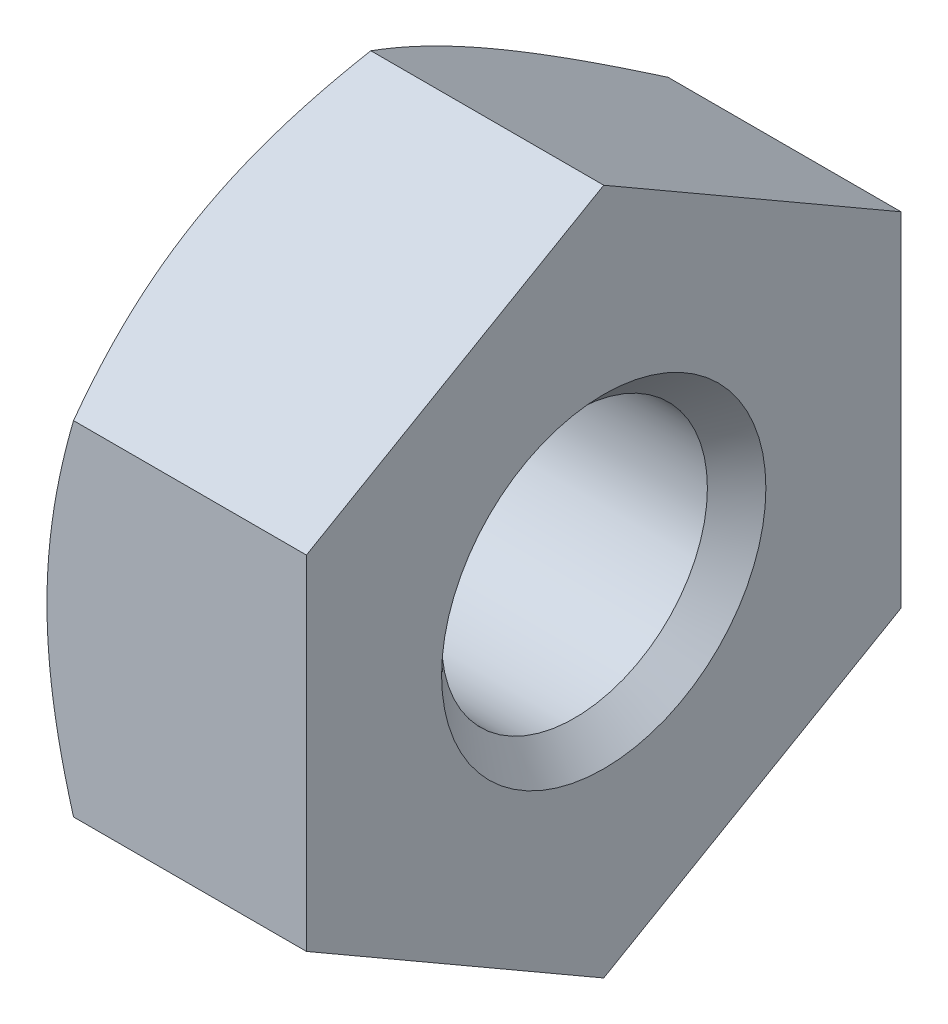
SolidWorks part; units mm, degrees
material "AISI 304"
ref_plane "正面" through (0, 0, 0) normal (0, 0, 1) x (1, 0, 0)
ref_plane "平面" through (0, 0, 0) normal (0, 1, 0) x (1, 0, 0)
ref_plane "右側面" through (0, 0, 0) normal (1, 0, 0) x (0, 0, -1)
ref_plane "Plane1" through (0, 0, 0) normal (0, 0, 1) x (1, 0, 0)
sketch "Sketch1" plane through (0, 0, 0) normal (0, 0, 1) x (1, 0, 0)
  line L0 (-1.2, 0) -> (-1.2, 2.75)
  line L1 (-1.2, 2.75) -> (-0.9402, 3.2)
  line L2 (-0.9402, 3.2) -> (1.2, 3.2)
  line L3 (1.2, 3.2) -> (1.2, 0)
  line L4 (1.2, 0) -> (-1.2, 0)
  line L5 (1.2, 0) -> (-1.2, 0) construction
revolve "Revolve1" add sketch "Sketch1" angle 360 about L5 reverse direction yes
ref_plane "Plane2" through (0, 0, 0) normal (0, 0, 1) x (1, 0, 0)
sketch "Sketch2" plane through (0, 0, 0) normal (0, 0, 1) x (1, 0, 0)
  line L0 (-1.2, 0) -> (-1.2, 1.5)
  line L1 (-1.2, 1.5) -> (-0.9295, 1.2295)
  line L2 (-0.9295, 1.2295) -> (0.9295, 1.2295)
  line L3 (0.9295, 1.2295) -> (1.2, 1.5)
  line L4 (1.2, 1.5) -> (1.2, 0)
  line L5 (1.2, 0) -> (-1.2, 0)
  line L6 (1.2, 0) -> (-1.2, 0) construction
revolve "Cut-Revolve1" cut sketch "Sketch2" angle 360 about L6 reverse direction yes
ref_plane "Plane3" through (0, 0, 0) normal (1, 0, 0) x (0, 0, -1)
sketch "Sketch3" plane through (0, 0, 0) normal (1, 0, 0) x (0, 0, -1)
  line L0 (-5.5, -5.5) -> (5.5, -5.5)
  line L1 (5.5, -5.5) -> (5.5, 5.5)
  line L2 (5.5, 5.5) -> (-5.5, 5.5)
  line L3 (-5.5, 5.5) -> (-5.5, -5.5)
  line L4 (-2.75, -1.5877) -> (0, -3.1754)
  line L5 (0, -3.1754) -> (2.75, -1.5877)
  line L6 (2.75, -1.5877) -> (2.75, 1.5877)
  line L7 (2.75, 1.5877) -> (0, 3.1754)
  line L8 (0, 3.1754) -> (-2.75, 1.5877)
  line L9 (-2.75, 1.5877) -> (-2.75, -1.5877)
extrude "Cut-Extrude1" cut sketch "Sketch3" against normal blind 1.2 and the other way blind 1.2
